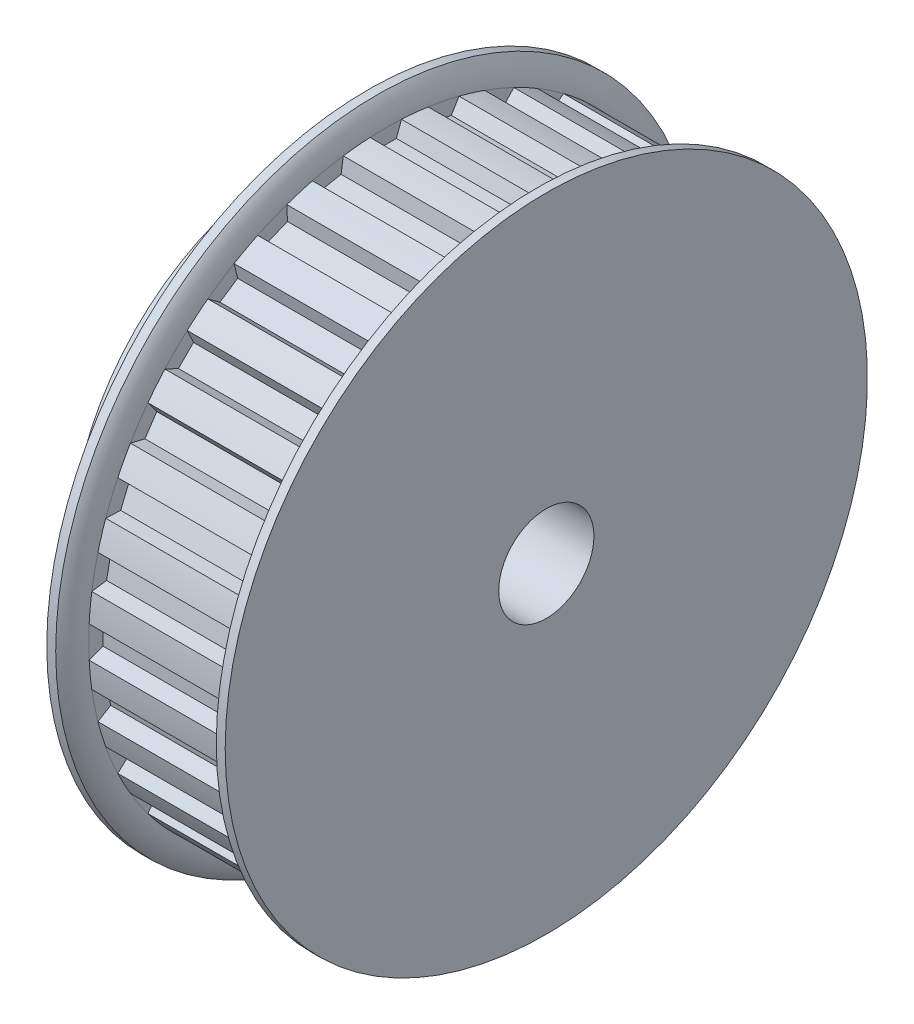
SolidWorks part; units mm, degrees
ref_plane "Front Plane" through (0, 0, 0) normal (0, 0, 1) x (1, 0, 0)
ref_plane "Top Plane" through (0, 0, 0) normal (0, 1, 0) x (1, 0, 0)
ref_plane "Right Plane" through (0, 0, 0) normal (1, 0, 0) x (0, 0, -1)
sketch "Sketch1" plane through (0, 0, 0) normal (1, 0, 0) x (0, 0, -1)
  line L3 (0, 0) -> (0, 23.77) construction
  line L6 (0, 23.77) -> (0, 24.97) construction
  line L7 (-1.325, 24.9348) -> (-0.8949, 23.7531)
  line L8 (1.325, 24.9348) -> (0.8949, 23.7531)
  line L9 (0, -2.2) -> (0, -3.2) construction
  line L10 (0, 25.47) -> (0, 24.97) construction
  line L12 (-0.8949, 23.7531) -> (0.8949, 23.7531)
  line L15 (0, 0) -> (0, -2.2) construction
  circle A0 centre (0, 0) radius 25.47 construction
  circle A1 centre (0, 0) radius 23.77 construction
  arc A7 (1.325, 24.9348) -> (-1.325, 24.9348) centre (0, 0) ccw
  dimension "PD" = 50.94
  dimension "D1" = 40
  dimension "D3" = 0.5
  dimension "D2" = 1.2
  dimension "D4" = 2.65
sketch "Sketch2" plane through (0, 0, 0) normal (0, 0, 1) x (1, 0, 0)
  line L0 (-10.5, 0) -> (10.5, 0) construction
  line L1 (-10.5, 4) -> (10.5, 4)
  line L2 (-10.5, 4) -> (-10.5, 19)
  line L3 (-4.5, 27) -> (-3.75, 27)
  line L4 (-3, 24.97) -> (-4.5, 24.97) construction
  line L5 (9.75, 24.97) -> (9.75, 27) construction
  line L6 (-3, 24.97) -> (9, 24.97)
  line L8 (9, 24.97) -> (10.5, 24.97) construction
  line L9 (9.75, 27) -> (10.5, 27)
  line L10 (10.5, 27) -> (10.5, 4)
  line L12 (-7.5, 19) -> (-7.5, 4) construction
  line L13 (-4.5, 27) -> (-4.5, 19)
  line L14 (-4.5, 19) -> (-10.5, 19)
  arc A0 (9, 24.97) -> (9.75, 27) centre (12.1223, 24.97) cw
  arc A1 (-3, 24.97) -> (-3.75, 27) centre (-6.1223, 24.97) ccw
  point P19 (-3, 24.97)
  point P20 (9, 24.97)
  dimension "Bore Size" = 8
  dimension "Overall Width" = 21
  dimension "Inside Width" = 12
  dimension "Outside Width" = 15
  dimension "Hub Dia" = 38
  dimension "OD" = 54
sketch "Sketch6" plane through (0, 0, 0) normal (0, 0, 1) x (1, 0, 0)
  line L0 (9.75, 27) -> (10.5, 27) construction
  line L1 (-3, 24.97) -> (9, 24.97) construction
  line L2 (-4.5, 27) -> (-3.75, 27) construction
  line L3 (-4.5, 27) -> (-4.5, 19) construction
  line L4 (-4.5, 19) -> (-10.5, 19) construction
  line L5 (-10.5, 4) -> (-10.5, 19) construction
  line L6 (-10.5, 4) -> (10.5, 4) construction
  line L7 (10.5, 27) -> (10.5, 4) construction
  line L8 (9.75, 27) -> (10.5, 27)
  line L9 (-3, 24.97) -> (9, 24.97)
  line L10 (-4.5, 27) -> (-3.75, 27)
  line L11 (-4.5, 27) -> (-4.5, 19)
  line L12 (-4.5, 19) -> (-10.5, 19)
  line L13 (-10.5, 4) -> (-10.5, 19)
  line L14 (-10.5, 4) -> (10.5, 4)
  line L15 (10.5, 27) -> (10.5, 4)
  arc A0 (9.75, 27) -> (9, 24.97) centre (12.1223, 24.97) ccw construction
  arc A1 (-3, 24.97) -> (-3.75, 27) centre (-6.1223, 24.97) ccw construction
  arc A2 (9.75, 27) -> (9, 24.97) centre (12.1223, 24.97) ccw
  arc A3 (-3, 24.97) -> (-3.75, 27) centre (-6.1223, 24.97) ccw
revolve "Revolve1" add sketch "Sketch6" angle 360 about L0
sketch "Sketch3" plane through (0, 0, 0) normal (1, 0, 0) x (0, 0, -1)
  line L2 (-1.325, 24.9348) -> (-0.8949, 23.7531) construction
  line L3 (-0.8949, 23.7531) -> (0.8949, 23.7531) construction
  line L4 (1.325, 24.9348) -> (0.8949, 23.7531) construction
  line L5 (-1.325, 24.9348) -> (-0.8949, 23.7531)
  line L6 (-0.8949, 23.7531) -> (0.8949, 23.7531)
  line L7 (1.325, 24.9348) -> (0.8949, 23.7531)
  arc A1 (1.325, 24.9348) -> (-1.325, 24.9348) centre (0, 0) ccw construction
  arc A2 (1.325, 24.9348) -> (-1.325, 24.9348) centre (0, 0) ccw
extrude "Cut-Extrude1" cut sketch "Sketch3" along normal up to vertex (9 mm away) from vertex up to point (9, 24.97, 0) starting at point (-3, 24.97, 0)
pattern_circular "CirPattern1" count 32 over 360 about axis through (-10.5, 0, 0) along (-1, 0, 0) of "Cut-Extrude1"
sketch "Sketch5" plane through (0, 0, 0) normal (0, 0, 1) x (1, 0, 0)
  line L0 (-10.5, 0) -> (10.5, 0) construction
  point P0 (9, 0)
ref_axis "Center Axis 1" through (10.5, 0, 0) along (-1, 0, 0)
equation "\"D3@Sketch1\" = \"ht@Sketch1\" / 2"
equation "\"D2@Sketch1\" = \"hs@Sketch1\" - \"ht@Sketch1\""
